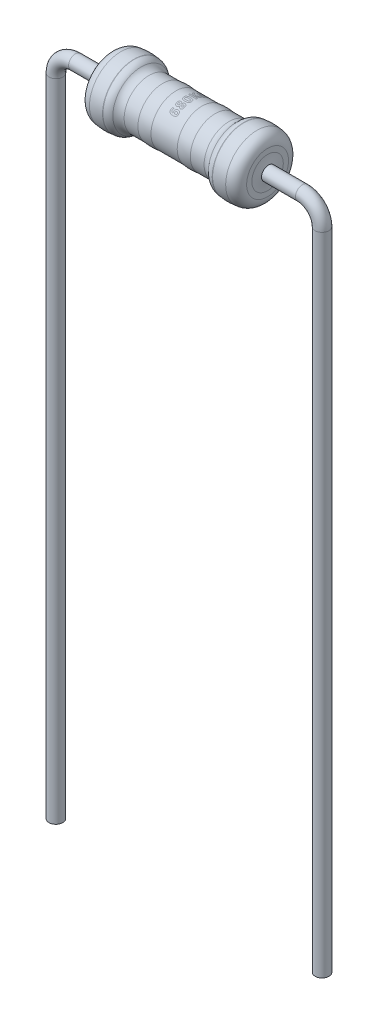
SolidWorks part; units mm, degrees
material "Plain Carbon Steel"
ref_plane "Front Plane" through (0, 0, 0) normal (0, 0, 1) x (1, 0, 0)
ref_plane "Top Plane" through (0, 0, 0) normal (0, 1, 0) x (1, 0, 0)
ref_plane "Right Plane" through (0, 0, 0) normal (1, 0, 0) x (0, 0, -1)
sketch "Sketch1" plane through (0, 0, 0) normal (0, 0, 1) x (1, 0, 0)
  line L0 (-4.33, 0) -> (4.33, 0)
  line L1 (-5.08, -0.75) -> (-5.08, -25.4)
  line L2 (5.08, -0.75) -> (5.08, -25.4)
  line L3 (-5.08, -25.4) -> (5.08, -25.4) construction
  line L4 (0, 0) -> (0, -25.4) construction
  arc A0 (-4.33, 0) -> (-5.08, -0.75) centre (-4.33, -0.75) ccw
  arc A1 (4.33, 0) -> (5.08, -0.75) centre (4.33, -0.75) cw
  dimension "D2" = 0.75
  dimension "D1" = 10.16
  dimension "D3" = 25.4
ref_plane "Plane1" through (-5.08, -25.4, 0) normal (0, -1, 0) x (-1, 0, 0)
sketch "Sketch2" plane through (-5.08, -25.4, 0) normal (0, -1, 0) x (-1, 0, 0)
  circle A0 centre (0, 0) radius 0.265
  dimension "D1" = 0.53
sweep "Sweep1" add profiles "Sketch2" path "Sketch1"
sketch "Sketch3" plane through (0, 0, 0) normal (0, 0, 1) x (1, 0, 0)
  line L0 (-3, 0) -> (3, 0)
  line L5 (-3, 0) -> (-3, 1.2)
  line L6 (3, 0) -> (3, 1.2)
  line L7 (-3, 1.2) -> (-1.75, 1.2)
  line L8 (3, 1.2) -> (1.75, 1.2)
  line L9 (-1.75, 1.2) -> (-1.75, 0.95)
  line L10 (-1.75, 0.95) -> (1.75, 0.95)
  line L11 (1.75, 0.95) -> (1.75, 1.2)
  line L12 (0, 0) -> (0, 0.95) construction
  dimension "D1" = 6
  dimension "D2" = 1.2
  dimension "D3" = 3.5
  dimension "D4" = 0.95
  dimension "D5" = 0.25
revolve "Revolve1" add sketch "Sketch3" angle 360 about L0
fillet "Fillet-1" radius 0.35 2 edges at (1.75, 0, 1.2) (-1.75, 0, 1.2)
fillet "Fillet-2" radius 0.4 4 edges at (3, 0, 1.2) (-3, 0, 1.2) (1.75, 0, 0.95) (-1.75, 0, 0.95)
sketch "Sketch5" plane through (0, 0, 0) normal (0, 0, 1) x (1, 0, 0)
  line L16 (-3, 0) -> (3, 0) construction
  line L17 (-2.6, 1.2) -> (-2.1, 1.2) construction
  line L18 (-2.6, 1.2) -> (-2.6, 0)
  line L19 (-2.6, 0) -> (-2.1, 0)
  line L20 (-2.1, 1.2) -> (-2.1, 0)
  line L21 (-1.75, 0.95) -> (1.75, 0.95) construction
  line L22 (2.6, 1.2) -> (2.1, 1.2) construction
  line L23 (2.6, 1.2) -> (2.6, 0)
  line L24 (2.6, 0) -> (2.1, 0)
  line L25 (2.1, 1.2) -> (2.1, 0)
  line L26 (-0.5, 0.95) -> (-1, 0.95) construction
  line L27 (-0.5, 0.95) -> (-0.5, 0)
  line L28 (-0.5, 0) -> (-1, 0)
  line L29 (-1, 0.95) -> (-1, 0)
  line L30 (-2.35, 1.2) -> (-2.35, 1.22) construction
  line L31 (1, 0.95) -> (0.5, 0.95) construction
  line L32 (1, 0.95) -> (1, 0)
  line L33 (1, 0) -> (0.5, 0)
  line L34 (0.5, 0.95) -> (0.5, 0)
  line L35 (-0.75, 0.95) -> (-0.75, 0.97) construction
  line L36 (0.75, 0.95) -> (0.75, 0.97) construction
  line L37 (2.35, 1.2) -> (2.35, 1.22) construction
  line L48 (-3, 0) -> (-3, 0.6)
  line L49 (-3, 0) -> (-3, 1.2) construction
  line L50 (-3, 0) -> (-3.05, 0)
  line L51 (-3.05, 0) -> (-3.05, 0.2)
  line L52 (3, 0) -> (3.05, 0)
  line L53 (3.05, 0) -> (3.05, 0.2)
  line L54 (3, 0) -> (3, 0.6)
  line L55 (3, 0) -> (3, 1.2) construction
  arc A0 (-2.6, 1.2) -> (-2.1, 1.2) centre (-2.35, -0.3525) cw
  arc A1 (-1, 0.95) -> (-0.5, 0.95) centre (-0.75, -0.6025) cw
  arc A2 (0.5, 0.95) -> (1, 0.95) centre (0.75, -0.6025) cw
  arc A3 (2.1, 1.2) -> (2.6, 1.2) centre (2.35, -0.3525) cw
  arc A6 (-3, 0.6) -> (-3.05, 0.2) centre (-4.625, 0.6) cw
  arc A7 (3.05, 0.2) -> (3, 0.6) centre (4.625, 0.6) cw
  dimension "D4" = 0.02
  dimension "D5" = 0.05
  dimension "D7" = 0.6
  dimension "D1" = 0.5
  dimension "D2" = 0.5
  dimension "D3" = 0.5
  dimension "D6" = 0.2
revolve "Revolve3" add sketch "Sketch5" angle 360 about L19
ref_plane "Plane2" through (0, 2, 0) normal (0, 1, 0) x (1, 0, 0)
sketch "Sketch6" plane through (0, 2, 0) normal (0, 1, 0) x (1, 0, 0)
  line L0 (0, 0) -> (0.15, 0) construction
  line L1 (0.15, 0.95) -> (0.15, -0.95) construction
  line L2 (0.5, 0.95) -> (-0.5, 0.95) construction
  text T0 "680KΩ" font "Calibri" height 0.3
  dimension "D1" = 0.15
wrap "Wrap1" sketch "Sketch6" wrap type scribe source sketch "Sketch6" face at (-0.5, -0.95, 0)
